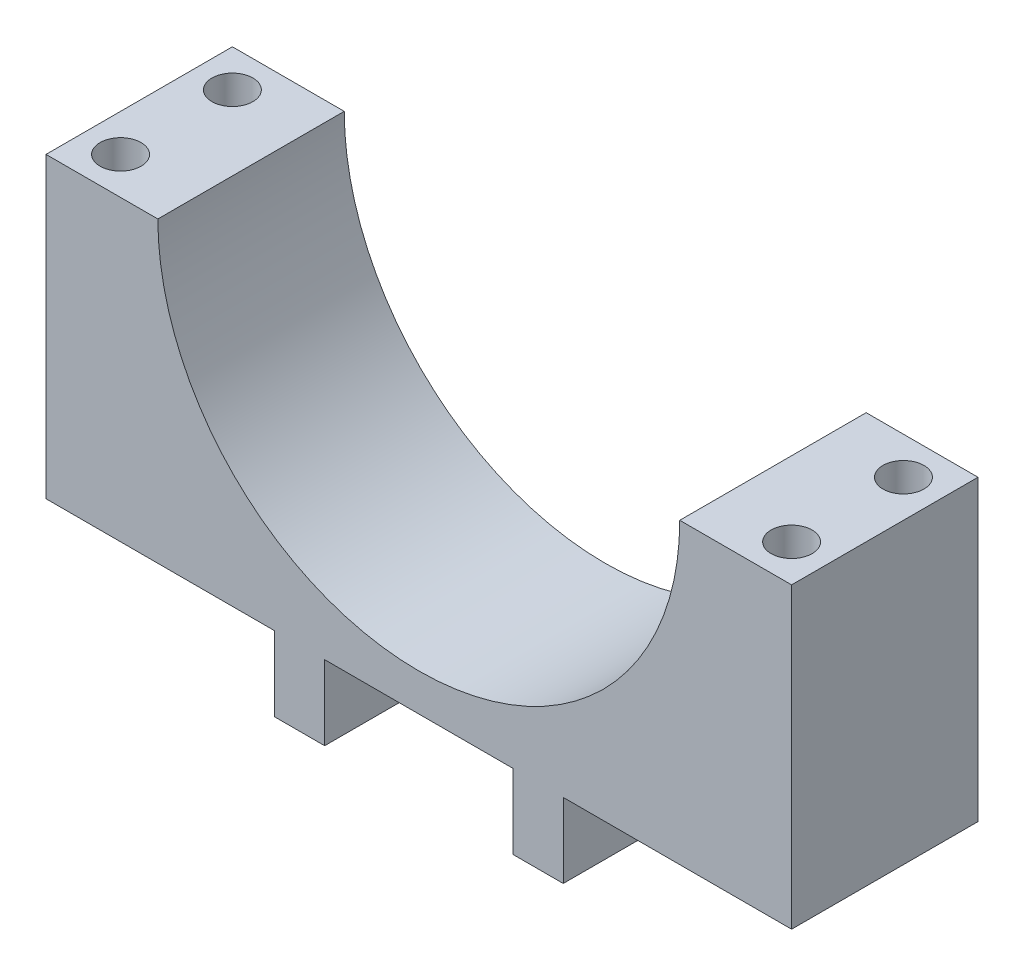
SolidWorks part; units mm, degrees
ref_plane "Płaszczyzna przednia" through (0, 0, 0) normal (0, 0, 1) x (1, 0, 0)
ref_plane "Płaszczyzna górna" through (0, 0, 0) normal (0, 1, 0) x (1, 0, 0)
ref_plane "Płaszczyzna prawa" through (0, 0, 0) normal (1, 0, 0) x (0, 0, -1)
sketch "Szkic1" plane through (0, 0, 0) normal (0, 0, 1) x (1, 0, 0)
  line L0 (70, 0) -> (100, 0)
  line L1 (100, 0) -> (100, -80)
  line L2 (100, -80) -> (38.75, -80)
  line L3 (38.75, -80) -> (38.75, -100)
  line L4 (38.75, -100) -> (25.25, -100)
  line L5 (25.25, -100) -> (25.25, -80)
  line L6 (25.25, -80) -> (-25.25, -80)
  line L7 (-25.25, -80) -> (-25.25, -100)
  line L8 (-25.25, -100) -> (-38.75, -100)
  line L9 (-38.75, -100) -> (-38.75, -80)
  line L10 (-38.75, -80) -> (-100, -80)
  line L11 (-100, -80) -> (-100, 0)
  line L12 (-100, 0) -> (-70, 0)
  line L13 (0, 27.9886) -> (0, -166.5804) construction
  arc A0 (70, 0) -> (-70, 0) centre (0, 0) cw
  point P19 (0, -80)
  dimension "D1" = 70
  dimension "D2" = 13.5
  dimension "D3" = 13.5
  dimension "D4" = 50.5
  dimension "D5" = 20
  dimension "D6" = 80
  dimension "D7" = 30
  dimension "D8" = 30
extrude "Dodanie-wyciągnięcie1" add sketch "Szkic1" along normal blind 50
ref_plane "Płaszczyzna1" through (0, 0, 0) normal (0, 1, 0) x (1, 0, 0)
sketch "Szkic2" plane through (0, 0, 0) normal (0, 1, 0) x (1, 0, 0)
  line L0 (-70, 0) -> (-100, 0) construction
  line L1 (-100, -50) -> (-100, 0) construction
  line L2 (-70, -50) -> (-100, -50) construction
  circle A0 centre (-90, -10) radius 5.5
  circle A1 centre (-90, -40) radius 5.5
  dimension "D1" = 10
  dimension "D3" = 10
  dimension "D2" = 10
  dimension "D4" = 10
extrude "Wytnij-wyciągnięcie1" cut sketch "Szkic2" against normal blind 21
mirror "Lustro1" about plane through (0, 0, 0) normal (1, 0, 0) of "Wytnij-wyciągnięcie1"
